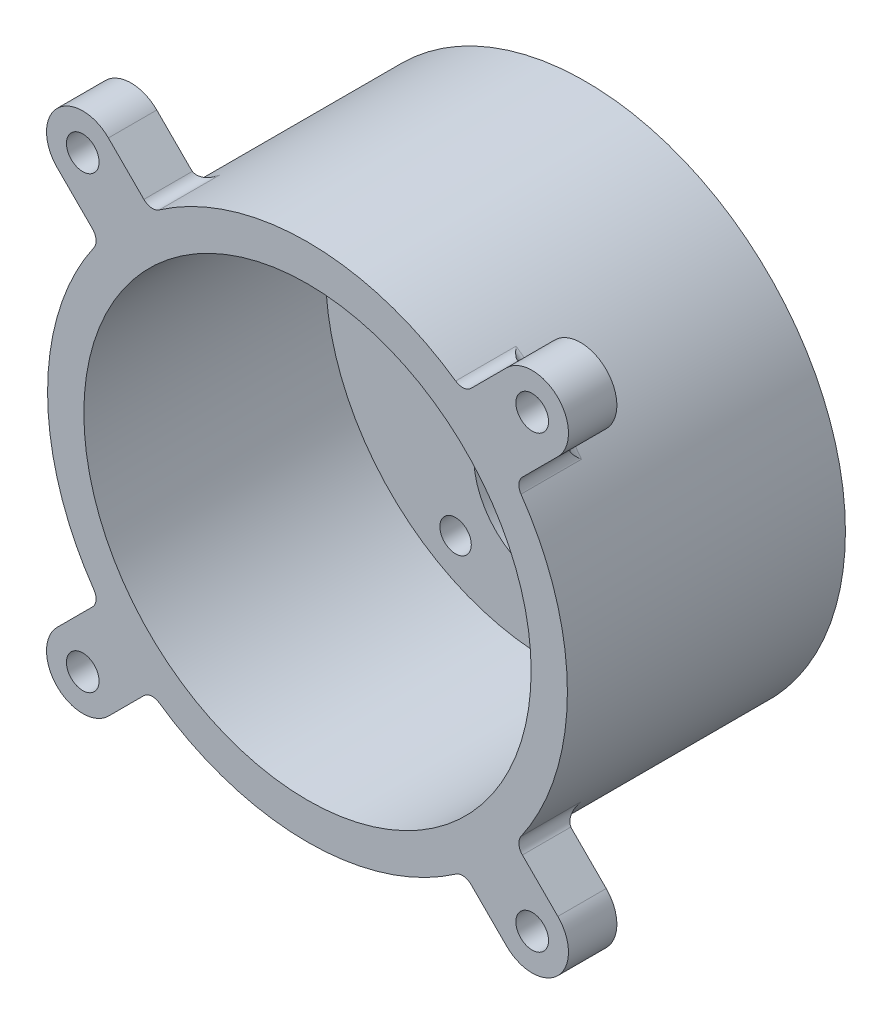
SolidWorks part; units mm, degrees
ref_plane "Front Plane" through (0, 0, 0) normal (0, 0, 1) x (1, 0, 0)
ref_plane "Top Plane" through (0, 0, 0) normal (0, 1, 0) x (1, 0, 0)
ref_plane "Right Plane" through (0, 0, 0) normal (1, 0, 0) x (0, 0, -1)
sketch "Sketch1" plane through (0, 0, 0) normal (0, 0, 1) x (1, 0, 0)
  circle A0 centre (0, 0) radius 18.5
  circle A1 centre (0, 0) radius 21.5
  dimension "D1" = 37
  dimension "D2" = 3
extrude "Boss-Extrude1" add sketch "Sketch1" along normal blind 3 contours A1 A0 | A0 region at (-20.8919, 0, 0)
extrude "Boss-Extrude2" add sketch "Sketch1<3>" along normal blind 20 from surface starting at face at (21.5, 0, 3)
sketch "Sketch1<3>" plane through (0, 0, 0) normal (0, 0, 1) x (1, 0, 0) same geometry as "Sketch1"
sketch "Sketch3" plane through (0, 0, 0) normal (0, 0, 1) x (1, 0, 0)
  circle A0 centre (0, -7) radius 6.25
  circle A1 centre (0, 0) radius 15.5 construction
  circle A2 centre (7.75, 13.4234) radius 1.3
  circle A3 centre (-7.75, 13.4234) radius 1.3
  circle A4 centre (15.5, 0) radius 1.3
  circle A5 centre (-15.5, 0) radius 1.3
  circle A6 centre (7.75, -13.4234) radius 1.3
  circle A7 centre (-7.75, -13.4234) radius 1.3
  dimension "D1" = 7
  dimension "D2" = 12.5
  dimension "D3" = 31
  dimension "D4" = 2.6
  dimension "D5" = 15.5
  dimension "D6" = 15.5
extrude "Cut-Extrude1" cut sketch "Sketch3" against normal through all both and the other way through all
sketch "Sketch4" plane through (0, 0, 0) normal (0, 0, 1) x (1, 0, 0)
  line L0 (25.5592, -25.5592) -> (-25.5592, 25.5592) construction
  line L1 (0, 0) -> (27.3207, 0) construction
  line L2 (-17.1754, 12.9327) -> (-20.7109, 16.4683)
  line L3 (-12.9327, 17.1754) -> (-16.4683, 20.7109)
  line L4 (0, 0) -> (0, 28.6929) construction
  line L5 (12.9327, 17.1754) -> (16.4683, 20.7109)
  line L6 (17.1754, 12.9327) -> (20.7109, 16.4683)
  line L7 (17.1754, -12.9327) -> (20.7109, -16.4683)
  line L8 (12.9327, -17.1754) -> (16.4683, -20.7109)
  line L9 (-12.9327, -17.1754) -> (-16.4683, -20.7109)
  line L10 (-17.1754, -12.9327) -> (-20.7109, -16.4683)
  circle A0 centre (0, 0) radius 21.5 construction
  arc A1 (-12.9327, 17.1754) -> (-17.1754, 12.9327) centre (0, 0) ccw
  arc A2 (-20.7109, 16.4683) -> (-20.7109, 20.7109) centre (-18.5896, 18.5896) cw
  arc A3 (-16.4683, 20.7109) -> (-20.7109, 20.7109) centre (-18.5896, 18.5896) ccw
  circle A4 centre (-18.5896, 18.5896) radius 1.35
  circle A5 centre (18.5896, 18.5896) radius 1.35
  arc A6 (16.4683, 20.7109) -> (20.7109, 20.7109) centre (18.5896, 18.5896) cw
  arc A7 (20.7109, 16.4683) -> (20.7109, 20.7109) centre (18.5896, 18.5896) ccw
  arc A8 (12.9327, 17.1754) -> (17.1754, 12.9327) centre (0, 0) cw
  arc A9 (12.9327, -17.1754) -> (17.1754, -12.9327) centre (0, 0) ccw
  arc A10 (20.7109, -16.4683) -> (20.7109, -20.7109) centre (18.5896, -18.5896) cw
  arc A11 (16.4683, -20.7109) -> (20.7109, -20.7109) centre (18.5896, -18.5896) ccw
  circle A12 centre (18.5896, -18.5896) radius 1.35
  circle A13 centre (-18.5896, -18.5896) radius 1.35
  arc A14 (-16.4683, -20.7109) -> (-20.7109, -20.7109) centre (-18.5896, -18.5896) cw
  arc A15 (-20.7109, -16.4683) -> (-20.7109, -20.7109) centre (-18.5896, -18.5896) ccw
  arc A16 (-12.9327, -17.1754) -> (-17.1754, -12.9327) centre (0, 0) cw
  point P3 (0, 0)
  dimension "D2" = 2.7
  dimension "D4" = 5
  dimension "D1" = 135
  dimension "D3" = 6
extrude "Boss-Extrude3" add sketch "Sketch4" against normal blind 4 from surface starting at face at (21.5, 0, 23)
fillet "Fillet1" radius 1 12 edges at (17.1754, 12.9327, 21) (12.9327, 17.1754, 21) (-12.9327, 17.1754, 21) (-17.1754, 12.9327, 21) (-17.1754, -12.9327, 21) (17.1754, -12.9327, 21) (-12.9327, -17.1754, 21) (12.9327, -17.1754, 21) (-15.2028, 15.2028, 19) (-15.2028, -15.2028, 19) (15.2028, -15.2028, 19) (15.2028, 15.2028, 19)
